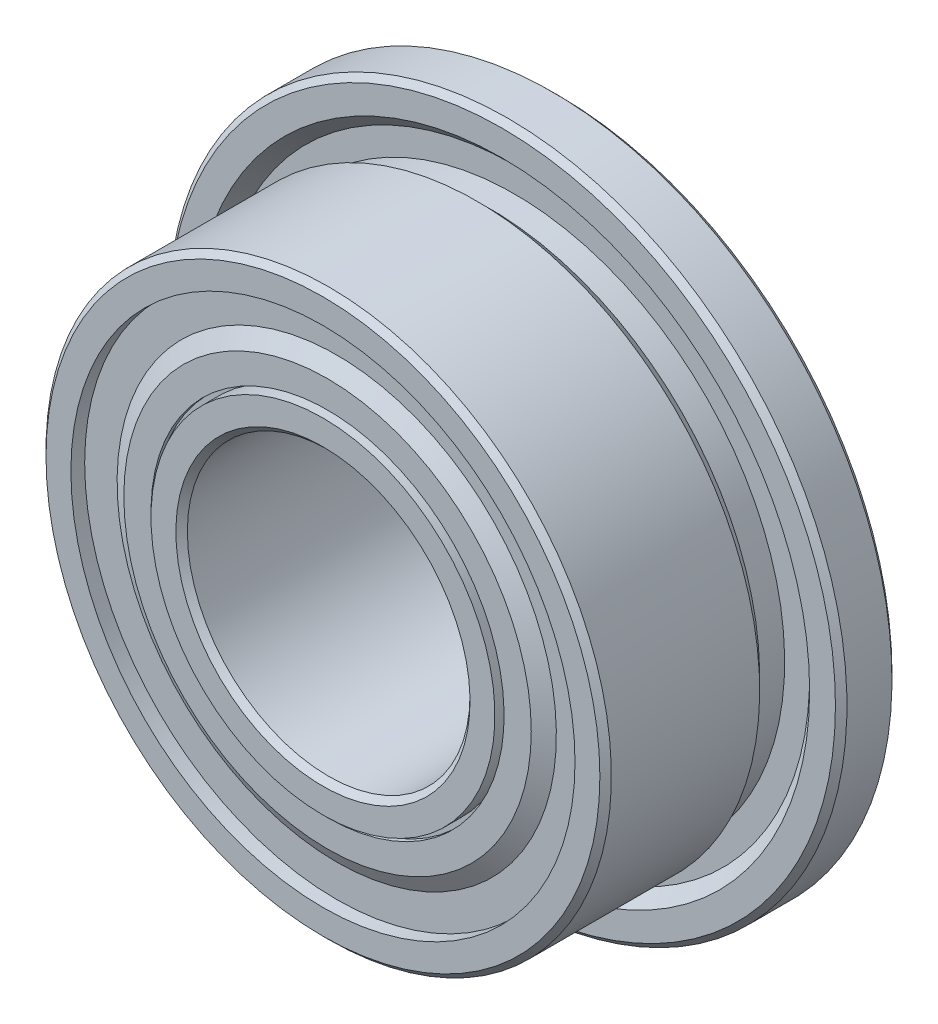
SolidWorks part; units mm, degrees
material "Alloy Steel"
ref_plane "Front Plane" through (0, 0, 0) normal (0, 0, 1) x (1, 0, 0)
ref_plane "Top Plane" through (0, 0, 0) normal (0, 1, 0) x (1, 0, 0)
ref_plane "Right Plane" through (0, 0, 0) normal (1, 0, 0) x (0, 0, -1)
sketch "Sketch1" plane through (0, 0, 0) normal (1, 0, 0) x (0, 0, -1)
  line L0 (0, 3) -> (0, -3) construction
  line L1 (-1.25, 3) -> (1.25, 3) construction
  line L2 (0, 0) -> (1.25, 0) construction
  line L3 (1.25, 3.6) -> (1.25, -3.6) construction
  line L4 (1.25, -3.6) -> (0.65, -3.6) construction
  line L5 (1.25, 1.5) -> (0, 1.5) construction
  line L6 (1.25, 1.5) -> (1.25, -1.5) construction
  dimension "OD" = 6
  dimension "Width" = 2.5
  dimension "Flange Thickness" = 0.6
  dimension "ID" = 3
  dimension "Flange OD" = 7.2
sketch "Sketch2" plane through (0, 0, 0) normal (1, 0, 0) x (0, 0, -1)
  line L0 (1.25, 3.6) -> (0.65, 3.6)
  line L1 (0.65, 3.6) -> (0.65, 3.2652)
  line L2 (0.3848, 3) -> (-1.25, 3)
  line L3 (-1.25, 3) -> (-1.25, 2.5125)
  line L4 (-1.25, 2.5125) -> (-0.3018, 2.5125)
  line L5 (1.25, 3.6) -> (1.25, -3.6) construction
  line L6 (1.25, 2.5125) -> (1.25, 3.6)
  line L7 (1.25, 1.5) -> (-1.25, 1.5)
  line L8 (-1.25, 1.5) -> (-1.25, 1.9875)
  line L9 (-1.25, 1.9875) -> (-0.3018, 1.9875)
  line L10 (1.25, 1.9875) -> (1.25, 1.5)
  line L11 (0, 3) -> (0, 1.5) construction
  line L12 (-0.4, 2.25) -> (0.4, 2.25) construction
  line L13 (0.3018, 2.5125) -> (1.25, 2.5125)
  line L14 (0.3018, 1.9875) -> (1.25, 1.9875)
  line L15 (0.65, 3.2652) -> (0.7826, 3.1326)
  line L16 (0.7826, 3.1326) -> (0.7826, 2.8674)
  line L17 (0.7826, 2.8674) -> (0.5174, 2.8674)
  line L18 (0.5174, 2.8674) -> (0.3848, 3)
  line L19 (0.65, 3) -> (0.7826, 2.8674) construction
  line L20 (0.7826, 3.1326) -> (0.5174, 2.8674) construction
  line L21 (0.3848, 3) -> (0.65, 3) construction
  line L22 (0.65, 3) -> (0.65, 3.2652) construction
  line L23 (-1.25, 0) -> (1.25, 0) construction
  circle A0 centre (0, 2.25) radius 0.4 construction
  arc A1 (-0.3018, 2.5125) -> (0.3018, 2.5125) centre (0, 2.25) cw
  arc A2 (-0.3018, 1.9875) -> (0.3018, 1.9875) centre (0, 2.25) ccw
  dimension "Ball Dia." = 0.8
  dimension "D2" = 135
  dimension "D3" = 0.375
  dimension "Race Thikness" = 0.4875
  dimension "D4" = 0.525
revolve "Revolve1" add sketch "Sketch2" angle 360 about L2
fillet "Fillet1" radius 0.0609 3 edges at (0, -3.6, -1.25) (0, -3.6, -0.65) (0, -3, 1.25) profile chamfer
sketch "Sketch3" plane through (0, 0, 0) normal (0, 0, 1) x (1, 0, 0)
  line L0 (-1.5, 0) -> (1.5, 0) construction
  line L1 (-3, 0) -> (3, 0) construction
  point P5 (0, 0)
  dimension "ID2" = 3
  dimension "OD2" = 6
fillet "Fillet2" radius 0.0609 2 edges at (0, -1.5, -1.25) (0, -1.5, 1.25) profile chamfer
sketch "Sketch7" plane through (0, 0, 0) normal (0, 0, 1) x (1, 0, 0)
  line L0 (0, 2.65) -> (0, 1.85)
  line L1 (0, 3.6) -> (0, -3.6) construction
  line L2 (-0.4787, 2.65) -> (0, 0) construction
  line L3 (0, 0) -> (0.4787, 2.65) construction
  line L4 (0.4787, 2.65) -> (-0.4787, 2.65) construction
  circle A0 centre (0, 2.25) radius 0.4 construction
  circle A1 centre (0, 0) radius 2.65 construction
  circle A2 centre (0, 0) radius 1.85 construction
  arc A4 (0, 2.65) -> (0, 1.85) centre (0, 2.25) ccw
  dimension "D1" = 20.481
revolve "Revolve3" add sketch "Sketch7" angle 360 about L0
pattern_circular "CirPattern3" count 14 over 360 about axis through (0, 0, 0) along (0, 0, -1) of bodies 107
sketch "Sketch8" plane through (0, 0, 0) normal (1, 0, 0) x (0, 0, -1)
  line L1 (-1.25, 2.5125) -> (-1.055, 2.5125)
  line L2 (-1.25, 2.5125) -> (-1.25, 2.675)
  line L3 (-1.25, 2.675) -> (-1.055, 2.675)
  line L4 (-1.055, 2.5125) -> (-1.055, 2.675)
  line L5 (1.25, 2.5125) -> (1.055, 2.5125)
  line L6 (1.25, 2.5125) -> (1.25, 2.675)
  line L7 (1.25, 2.675) -> (1.055, 2.675)
  line L8 (1.055, 2.5125) -> (1.055, 2.675)
  line L9 (1.25, 1.9875) -> (1.055, 1.9875)
  line L10 (1.25, 1.9875) -> (1.25, 1.825)
  line L11 (1.25, 1.825) -> (1.055, 1.825)
  line L12 (1.055, 1.9875) -> (1.055, 1.825)
  line L13 (-1.25, 1.9875) -> (-1.055, 1.9875)
  line L14 (-1.25, 1.9875) -> (-1.25, 1.825)
  line L15 (-1.25, 1.825) -> (-1.055, 1.825)
  line L16 (-1.055, 1.9875) -> (-1.055, 1.825)
  dimension "D1" = 0.1625
  dimension "D2" = 0.195
revolve "Cut-Revolve1" cut sketch "Sketch8" angle 360 about L2
sketch "Sketch9" plane through (0, 0, 0) normal (1, 0, 0) x (0, 0, -1)
  line L0 (-1.055, 2.675) -> (-1.055, 2.3179)
  line L1 (-1.055, 2.3179) -> (-1.1525, 2.149)
  line L2 (-1.1525, 2.149) -> (-1.1525, 1.8737)
  line L3 (1.1525, 1.8738) -> (1.1525, 1.825) construction
  line L4 (1.055, 2.675) -> (1.055, 2.3179)
  line L5 (1.055, 2.3179) -> (1.1525, 2.149)
  line L6 (1.1525, 2.149) -> (1.1525, 1.8738)
  line L7 (1.25, 1.825) -> (1.055, 1.825) construction
  line L8 (-1.1037, 2.675) -> (-1.1037, 2.3309)
  line L9 (-1.1037, 2.3309) -> (-1.2012, 2.162)
  line L10 (-1.2012, 2.162) -> (-1.2012, 1.8737)
  line L11 (-1.055, 2.675) -> (-1.1037, 2.675)
  line L12 (-1.1525, 1.8737) -> (-1.2012, 1.8737)
  line L13 (1.1038, 2.675) -> (1.1038, 2.3309)
  line L14 (1.1038, 2.3309) -> (1.2013, 2.162)
  line L15 (1.2013, 2.162) -> (1.2013, 1.8738)
  line L16 (1.055, 2.675) -> (1.1038, 2.675)
  line L17 (1.1525, 1.8738) -> (1.2013, 1.8738)
  line L18 (-1.055, 2.3179) -> (-1.055, 2.5308) construction
  line L19 (1.055, 2.3179) -> (1.055, 2.675) construction
  line L20 (-1.055, 1.825) -> (-1.25, 1.825) construction
  line L22 (-1.1525, 1.8737) -> (-1.1525, 1.825) construction
  dimension "D2" = 150
  dimension "D1" = 150
  dimension "D5" = 0.195
  dimension "D3" = 0.0488
  dimension "D4" = 0.0488
  dimension "D6" = 0.3571
revolve "Revolve4" add sketch "Sketch9" angle 360 about L2
equation "\"D1@Fillet1\"=\"Race Thikness@Sketch2\"/8"
equation "\"ID2@Sketch3\" = \"ID@Sketch1\""
equation "\"OD2@Sketch3\" = \"OD@Sketch1\""
equation "\"D1@Fillet2\"=\"Race Thikness@Sketch2\"/8"
equation "\"D1@CirPattern3\"=360/\"D1@Sketch7\"-4"
equation "\"D1@Sketch8\"=\"Race Thikness@Sketch2\"/3"
equation "\"D2@Sketch8\"=\"Race Thikness@Sketch2\"/2.5"
equation "\"D3@Sketch9\"=\"D5@Sketch9\"/4"
equation "\"D4@Sketch9\"=\"D5@Sketch9\"/4"
equation "\"D1@Sketch9\"=\"D2@Sketch9\""
equation "\"Ball Dia.@Sketch2\" = \"D1@Sketch2\"*.5"
equation "\"D4@Sketch2\"=((\"OD@Sketch1\"-\"ID@Sketch1\")/2)*.35"
